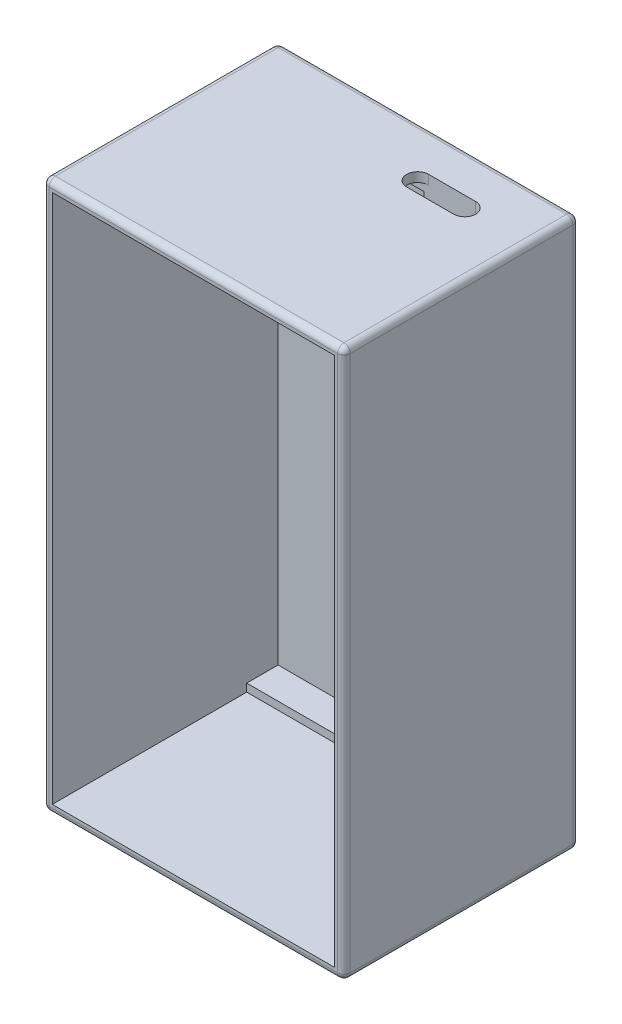
SolidWorks part; units mm, degrees
ref_plane "Front Plane" through (0, 0, 0) normal (0, 0, 1) x (1, 0, 0)
ref_plane "Top Plane" through (0, 0, 0) normal (0, 1, 0) x (1, 0, 0)
ref_plane "Right Plane" through (0, 0, 0) normal (1, 0, 0) x (0, 0, -1)
sketch "Sketch1" plane through (0, 0, 0) normal (0, 0, 1) x (1, 0, 0)
  line L1 (48, 87.5) -> (-48, 87.5)
  line L2 (48, 87.5) -> (48, -87.5)
  line L3 (48, -87.5) -> (-48, -87.5)
  line L4 (-48, 87.5) -> (-48, -87.5)
  line L5 (48, 87.5) -> (-48, -87.5) construction
  line L6 (48, -87.5) -> (-48, 87.5) construction
  point P0 (0, 0)
  dimension "D1" = 175
  dimension "D2" = 96
extrude "Boss-Extrude1" add sketch "Sketch1" along normal blind 100
sketch "Sketch2" plane through (0, 0, 100) normal (0, 0, 1) x (1, 0, 0)
  line L0 (-48, 87.5) -> (-48, -87.5) construction
  line L1 (45, 84.5) -> (-45, 84.5)
  line L2 (45, 84.5) -> (45, -84.5)
  line L3 (45, -84.5) -> (-45, -84.5)
  line L4 (-45, 84.5) -> (-45, -84.5)
  line L5 (45, 84.5) -> (-45, -84.5) construction
  line L6 (45, -84.5) -> (-45, 84.5) construction
  line L8 (-48, -87.5) -> (48, -87.5) construction
  point P0 (0, 0)
  dimension "D1" = 3
  dimension "D2" = 3
extrude "Cut-Extrude1" cut sketch "Sketch2" against normal blind 87
sketch "Sketch3" plane through (0, 0, 13) normal (0, 0, 1) x (1, 0, 0)
  line L0 (-45, 84.5) -> (-45, -84.5) construction
  line L1 (-45, 82) -> (11.5, 82)
  line L2 (-45, 82) -> (-45, -82)
  line L3 (-45, -82) -> (11.5, -82)
  line L4 (11.5, 82) -> (11.5, -82)
  line L5 (-45, -84.5) -> (45, -84.5) construction
  line L6 (45, 84.5) -> (-45, 84.5) construction
  dimension "D1" = 2.5
  dimension "D2" = 2.5
  dimension "D3" = 56.5
extrude "Cut-Extrude2" cut sketch "Sketch3" against normal blind 10
sketch "Sketch4" plane through (0, 0, 13) normal (0, 0, 1) x (1, 0, 0)
  line L0 (11.5, -72.6234) -> (45, -72.6234) construction
  line L1 (11.5, -82) -> (11.5, 82) construction
  line L2 (45, -84.5) -> (45, 84.5) construction
  line L3 (28.25, -72.6234) -> (28.25, -84.5) construction
  line L4 (-45, -84.5) -> (45, -84.5) construction
sketch "Sketch5" plane through (0, -84.5, 0) normal (0, 1, 0) x (1, 0, 0)
  line L0 (28.25, -13) -> (28.25, -23) construction
  circle A0 centre (28.25, -23) radius 6
  dimension "D2" = 12
  dimension "D1" = 10
extrude "Cut-Extrude3" cut sketch "Sketch5" against normal blind 10
sketch "Sketch6" plane through (0, 0, 13) normal (0, 0, 1) x (1, 0, 0)
  line L0 (45, -84.5) -> (45, 84.5) construction
  line L1 (28.25, -84.5) -> (28.25, -39.5) construction
  line L2 (45, -39.5) -> (11.5, -39.5)
  line L3 (45, -39.5) -> (45, 8.5)
  line L4 (45, 8.5) -> (11.5, 8.5)
  line L5 (11.5, -39.5) -> (11.5, 8.5)
  line L6 (11.5, -82) -> (11.5, 82) construction
  dimension "D1" = 45
  dimension "D2" = 48
extrude "Cut-Extrude4" cut sketch "Sketch6" against normal blind 10
sketch "Sketch7" plane through (0, 0, 13) normal (0, 0, 1) x (1, 0, 0)
  line L0 (45, 84.5) -> (13, 84.5) construction
  line L1 (45, 84.5) -> (-45, 84.5) construction
  dimension "D1" = 32
sketch "Sketch9" plane through (0, 84.5, 0) normal (0, -1, 0) x (1, 0, 0)
  line L0 (13, 13) -> (13, 16.5) construction
  line L1 (13, 16.5) -> (28, 16.5) construction
  line L2 (13, 20) -> (28, 20)
  line L3 (13, 13) -> (28, 13)
  arc A0 (13, 20) -> (13, 13) centre (13, 16.5) ccw
  arc A1 (28, 13) -> (28, 20) centre (28, 16.5) ccw
  point P3 (20.5, 16.5)
  dimension "D1" = 3.5
  dimension "D2" = 15
  dimension "D3" = 7
extrude "Cut-Extrude6" cut sketch "Sketch9" against normal blind 10
sketch "Sketch10" plane through (0, -87.5, 0) normal (0, -1, 0) x (1, 0, 0)
  line L0 (48, 100) -> (48, 0) construction
  line L1 (-48, 100) -> (48, 100)
  line L2 (-48, 100) -> (-48, 75)
  line L3 (-48, 75) -> (48, 75)
  line L4 (48, 100) -> (48, 75)
  dimension "D1" = 25
extrude "Cut-Extrude8" cut sketch "Sketch10" against normal blind 200
fillet "Fillet1" radius 2 12 edges at (0, 87.5, 0) (0, 87.5, 75) (48, 87.5, 37.5) (48, 0, 0) (48, 0, 75) (-48, 87.5, 37.5) (-48, 0, 75) (-48, 0, 0) (0, -87.5, 75) (48, -87.5, 37.5) (0, -87.5, 0) (-48, -87.5, 37.5)
sketch "Sketch11" plane through (0, -87.5, 0) normal (0, -1, 0) x (1, 0, 0)
  line L0 (28.25, 23) -> (0, 23) construction
  circle A0 centre (0, 23) radius 2.5
  dimension "D1" = 5
extrude "Cut-Extrude9" cut sketch "Sketch11" against normal blind 5
